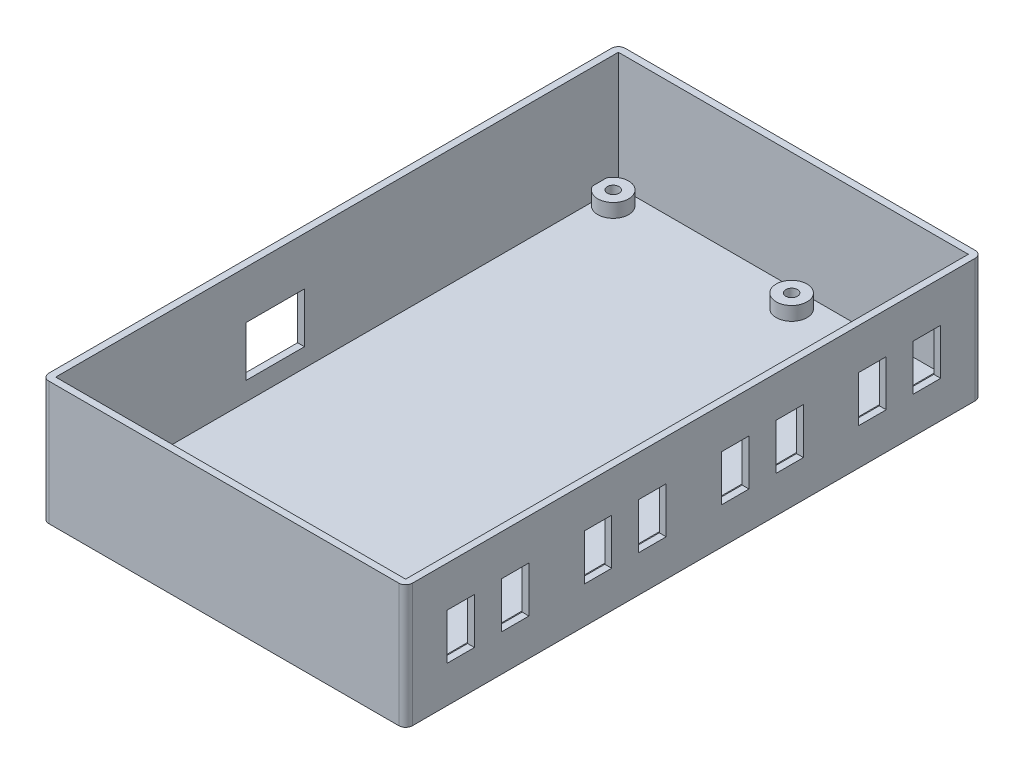
SolidWorks part; units mm, degrees
ref_plane "Ebene vorne" through (0, 0, 0) normal (0, 0, 1) x (1, 0, 0)
ref_plane "Ebene oben" through (0, 0, 0) normal (0, 1, 0) x (1, 0, 0)
ref_plane "Ebene rechts" through (0, 0, 0) normal (1, 0, 0) x (0, 0, -1)
sketch "Skizze1" plane through (0, 0, 0) normal (0, 1, 0) x (1, 0, 0)
  line L1 (0, 0) -> (106, 0)
  line L2 (0, 0) -> (0, 168)
  line L3 (0, 168) -> (106, 168)
  line L4 (106, 0) -> (106, 168)
  dimension "D1" = 106
  dimension "D2" = 168
extrude "Aufsatz-Linear austragen1" add sketch "Skizze1" along normal blind 36
shell "Wandung1" thickness 2 removed face at (53, 36, -84)
sketch "Skizze2" plane through (0, 2, 0) normal (0, 1, 0) x (1, 0, 0)
  line L1 (6, 7.5) -> (58, 7.5) construction
  line L2 (6, 7.5) -> (6, 160.5) construction
  line L3 (6, 160.5) -> (58, 160.5) construction
  line L4 (58, 7.5) -> (58, 160.5) construction
  line L6 (2, 166) -> (2, 2) construction
  line L7 (2, 2) -> (104, 2) construction
  circle A0 centre (6, 7.5) radius 4.5
  circle A1 centre (58, 7.5) radius 4.5
  circle A2 centre (58, 160.5) radius 4.5
  circle A3 centre (6, 160.5) radius 4.5
  dimension "D5" = 9
  dimension "D1" = 153
  dimension "D2" = 52
  dimension "D3" = 4
  dimension "D4" = 5.5
  dimension "D6" = 2
  dimension "D7" = 2
extrude "Aufsatz-Linear austragen2" add sketch "Skizze2" along normal blind 4
fillet "Verrundung1" radius 2 4 edges at (0, 18, -168) (106, 18, -168) (106, 18, 0) (0, 18, 0)
hole_wizard "Stirnsenkung für M3 Zylinderschraube mit Innensechskant1" positions "Skizze5" profile "Skizze6" counterbore size "M3" standard "DIN"
sketch "Skizze5" plane through (0, 0, 0) normal (0, -1, 0) x (-1, 0, 0)
  line L1 (-58, 7.5) -> (-6, 7.5) construction
  line L2 (-58, 7.5) -> (-58, 160.5) construction
  line L3 (-58, 160.5) -> (-6, 160.5) construction
  line L4 (-6, 7.5) -> (-6, 160.5) construction
  line L5 (-2, 0) -> (-104, 0) construction
  line L7 (0, 166) -> (0, 2) construction
  point P0 (-58, 7.5)
  point P1 (-6, 160.5)
  point P100 (-58, 160.5)
  point P101 (-6, 7.5)
  dimension "D1" = 52
  dimension "D2" = 153
  dimension "D3" = 7.5
  dimension "D4" = 6
sketch "Skizze6" plane through (58, 0, -7.5) normal (1, 0, 0) x (0, 0, -1)
  line L0 (0, 0) -> (0, 15.0215)
  line L1 (0, 15.0215) -> (1.7, 14)
  line L2 (1.7, 14) -> (1.7, 3.4)
  line L3 (1.7, 3.4) -> (3.25, 3.4)
  line L5 (3.25, 3.4) -> (3.25, 0.025)
  line L6 (3.25, 0.025) -> (3.275, 0)
  line L7 (3.275, 0) -> (0, 0)
  line L8 (-3.25, 0.025) -> (-3.275, 0) construction
  line L10 (0, 15.0215) -> (-1.7, 14) construction
  line L11 (0, -6.35) -> (0, 107.95) construction
  dimension "Bohrerdurchmesser" = 3.4
  dimension "Bohrungstiefe" = 14
  dimension "Senkdurchmesser2" = 6.5
  dimension "Senktiefe2" = 3.4
  dimension "Senkdurchmesser4 (Oben)" = 6.55
  dimension "Senkwinkel2 (Oben)" = 90
  dimension "Spitzenwinkel" = 118
sketch "Skizze7" plane through (0, 0, 0) normal (-1, 0, 0) x (0, 0, 1)
  line L0 (0, 36) -> (0, 0) construction
  line L1 (-74.5, 22.02) -> (-57.5, 22.02)
  line L2 (-74.5, 22.02) -> (-74.5, 7.42)
  line L3 (-74.5, 7.42) -> (-57.5, 7.42)
  line L4 (-57.5, 22.02) -> (-57.5, 7.42)
  line L5 (-74.5, 22.02) -> (-57.5, 7.42) construction
  line L6 (-74.5, 7.42) -> (-57.5, 22.02) construction
  line L7 (-166, 0) -> (-2, 0) construction
  point P0 (-66, 14.72)
  dimension "D1" = 17
  dimension "D2" = 14.6
  dimension "D3" = 57.5
  dimension "D4" = 7.42
extrude "Schnitt-Linear austragen1" cut sketch "Skizze7" against normal blind 10
sketch "Skizze8" plane through (106, 0, 0) normal (1, 0, 0) x (0, 0, -1)
  line L0 (2, 0) -> (166, 0) construction
  line L1 (12.06, 24.12) -> (20.06, 24.12)
  line L2 (12.06, 24.12) -> (12.06, 10.72)
  line L3 (12.06, 10.72) -> (20.06, 10.72)
  line L4 (20.06, 24.12) -> (20.06, 10.72)
  line L5 (12.06, 24.12) -> (20.06, 10.72) construction
  line L6 (12.06, 10.72) -> (20.06, 24.12) construction
  line L7 (0, 0) -> (0, 36) construction
  line L9 (27.94, 10.72) -> (35.94, 10.72)
  line L10 (27.94, 10.72) -> (27.94, 24.12)
  line L11 (27.94, 24.12) -> (35.94, 24.12)
  line L12 (35.94, 10.72) -> (35.94, 24.12)
  line L13 (27.94, 10.72) -> (35.94, 24.12) construction
  line L14 (27.94, 24.12) -> (35.94, 10.72) construction
  point P0 (16.06, 17.42)
  point P9 (31.94, 17.42)
  dimension "D1" = 8
  dimension "D2" = 13.4
  dimension "D3" = 10.72
  dimension "D4" = 12.06
  dimension "D5" = 7.88
  dimension "D6" = 8
  dimension "D7" = 13.4
  dimension "D8" = 10.72
extrude "Schnitt-Linear austragen2" cut sketch "Skizze8" against normal blind 10
sketch "Skizze9" plane through (0, 2, 0) normal (0, 1, 0) x (1, 0, 0)
  line L0 (2, 2) -> (104, 2) construction
  line L1 (104, 166) -> (99, 166)
  line L2 (104, 166) -> (104, 2)
  line L3 (104, 2) -> (99, 2)
  line L4 (99, 166) -> (99, 2)
  dimension "D1" = 5
extrude "Aufsatz-Linear austragen3" add sketch "Skizze9" along normal blind 4
pattern_linear "Lineares Muster1" count 4 spacing 40 along (0, 0, -1) of "Schnitt-Linear austragen2"
